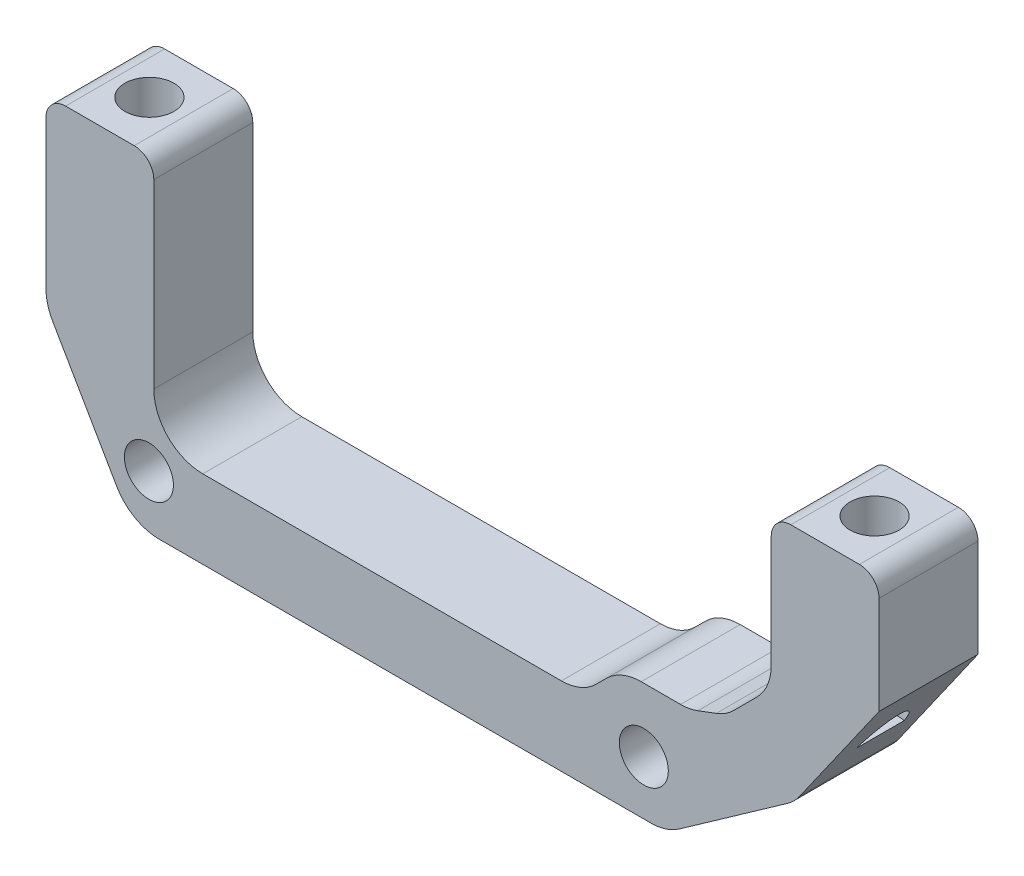
SolidWorks part; units mm, degrees
ref_plane "Front Plane" through (0, 0, 0) normal (0, 0, 1) x (1, 0, 0)
ref_plane "Top Plane" through (0, 0, 0) normal (0, 1, 0) x (1, 0, 0)
ref_plane "Right Plane" through (0, 0, 0) normal (1, 0, 0) x (0, 0, -1)
sketch "Sketch1" plane through (0, 0, 0) normal (0, 0, 1) x (1, 0, 0)
  line L0 (-31.5, 16.75) -> (-31.5, -8.75)
  line L1 (-31.5, -8.75) -> (12.1603, -8.75)
  line L2 (12.1603, -8.75) -> (16.1603, -4.75)
  line L3 (16.1603, -4.75) -> (23.1603, -4.75)
  line L4 (23.1603, -4.75) -> (26.9038, -3.3408)
  line L5 (26.9038, -3.3408) -> (31.5, 1.2554)
  line L6 (31.5, 1.2554) -> (31.5, 16.75)
  line L7 (31.5, 16.75) -> (42.5, 16.75)
  line L8 (42.5, 16.75) -> (42.5, 4.75)
  line L10 (33.8846, -7.529) -> (20.8089, -16.75)
  line L11 (20.8089, -16.75) -> (-33.8397, -16.75)
  line L12 (-33.8397, -16.75) -> (-42.5, -1.75)
  line L13 (-42.5, -1.75) -> (-42.5, 16.75)
  line L14 (-42.5, 16.75) -> (-31.5, 16.75)
  line L15 (-31.5, 16.75) -> (31.5, 16.75) construction
  line L16 (0, 0) -> (0, 16.75) construction
  line L17 (0, 0) -> (0, -16.75) construction
  line L18 (33.8846, -7.529) -> (42.5, 4.75)
  line L19 (33.8846, -7.529) -> (29.2019, -1.0427) construction
  dimension "D1" = 11
  dimension "D2" = 11
  dimension "D3" = 33.5
  dimension "D4" = 85
  dimension "D5" = 8
  dimension "D6" = 150
  dimension "D7" = 16
  dimension "D8" = 18.5
  dimension "D9" = 12
  dimension "D10" = 15
  dimension "D11" = 46
  dimension "D12" = 4
  dimension "D13" = 6.5
  dimension "D14" = 4
  dimension "D15" = 135
  dimension "D16" = 7
  dimension "D17" = 8
extrude "Boss-Extrude1" add sketch "Sketch1" along normal blind 5.05 and the other way blind 5.05
fillet "Fillet1" radius 5 10 edges at (31.5, 1.2554, 0) (26.9038, -3.3408, 0) (23.1603, -4.75, 0) (16.1603, -4.75, 0) (12.1603, -8.75, 0) (33.8846, -7.529, 0) (20.8089, -16.75, 0) (-33.8397, -16.75, 0) (-42.5, -1.75, 0) (-31.5, -8.75, 0)
sketch "Sketch2" plane through (0, 16.75, 0) normal (0, 1, 0) x (1, 0, 0)
  line L0 (-42.5, 5.05) -> (-31.5, -5.05) construction
  line L1 (42.5, 5.05) -> (31.5, -5.05) construction
  circle A0 centre (-37, 0) radius 2.5
  circle A1 centre (37, 0) radius 2.5
  point P12 (37, 0)
  point P13 (-37, 0)
  dimension "D1" = 5
extrude "Cut-Extrude1" cut sketch "Sketch2" against normal blind 19
fillet "Fillet2" radius 2 4 edges at (42.5, 16.75, 0) (31.5, 16.75, 0) (-31.5, 16.75, 0) (-42.5, 16.75, 0)
sketch "Sketch3" plane through (0, 0, 0) normal (0, 0, 1) x (1, 0, 0)
  line L0 (-32, -11.25) -> (18.5, -11.25) construction
  line L1 (-30.953, -16.75) -> (19.2232, -16.75) construction
  line L2 (-31.5, -3.75) -> (-31.5, 14.75) construction
  circle A0 centre (-32, -11.25) radius 2.5
  circle A1 centre (18.5, -11.25) radius 2.5
  dimension "D1" = 5
  dimension "D2" = 5.5
  dimension "D3" = 0.5
  dimension "D4" = 50.5
extrude "Cut-Extrude2" cut sketch "Sketch3" against normal through all both and the other way through all
